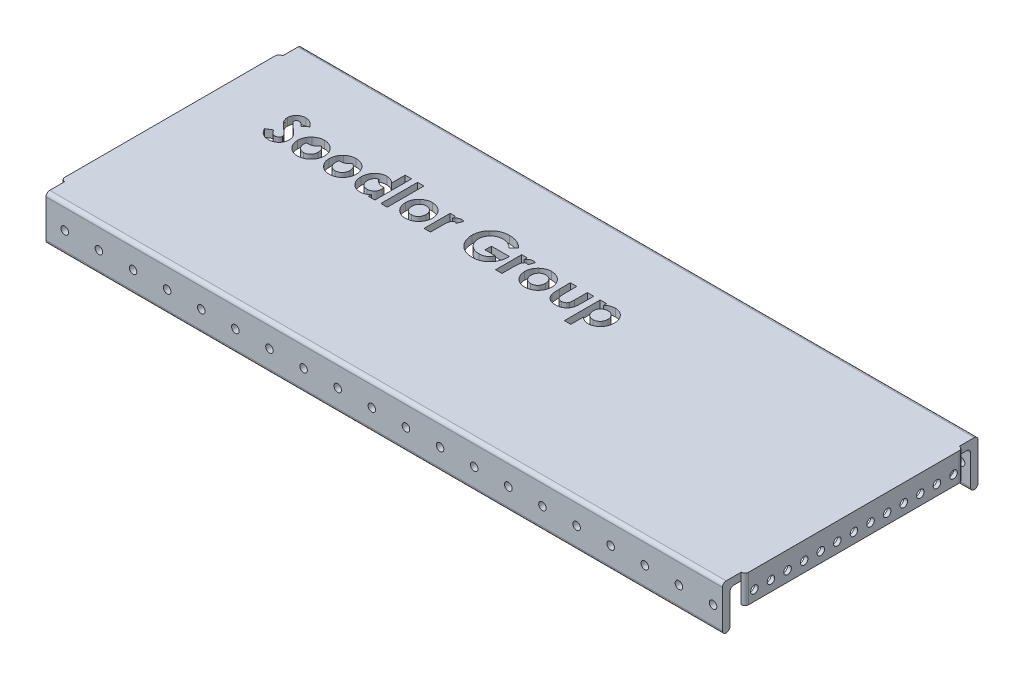
SolidWorks part; units mm, degrees
ref_plane "Front Plane" through (0, 0, 0) normal (0, 0, 1) x (1, 0, 0)
ref_plane "Top Plane" through (0, 0, 0) normal (0, 1, 0) x (1, 0, 0)
ref_plane "Right Plane" through (0, 0, 0) normal (1, 0, 0) x (0, 0, -1)
sketch "Sketch1" plane through (0, 0, 0) normal (0, 1, 0) x (1, 0, 0)
  line L1 (-180, 68.01) -> (180, 68.01)
  line L2 (-180, 68.01) -> (-180, -68.01)
  line L3 (-180, -68.01) -> (180, -68.01)
  line L4 (180, 68.01) -> (180, -68.01)
  line L5 (-180, 68.01) -> (180, -68.01) construction
  line L6 (-180, -68.01) -> (180, 68.01) construction
  point P0 (0, 0)
  dimension "D1" = 136.02
  dimension "D2" = 360
extrude "Boss-Extrude1" add sketch "Sketch1" along normal blind 4
sketch "Sketch2" plane through (0, 0, 0) normal (0, -1, 0) x (-1, 0, 0)
  line L0 (-180, -68.01) -> (-180, 68.01) construction
  line L1 (180, -68.01) -> (-180, -68.01)
  line L2 (180, -68.01) -> (180, -64.01)
  line L3 (180, -64.01) -> (-180, -64.01)
  line L4 (-180, -68.01) -> (-180, -64.01)
  line L6 (180, 68.01) -> (-180, 68.01)
  line L7 (180, 68.01) -> (180, 64.01)
  line L8 (180, 64.01) -> (-180, 64.01)
  line L9 (-180, 68.01) -> (-180, 64.01)
  dimension "D1" = 4
  dimension "D2" = 4
extrude "Boss-Extrude2" add sketch "Sketch2" along normal blind 20
fillet "Fillet1" radius 2 8 edges at (0, 0, -64.01) (0, 0, 64.01) (0, -20, 64.01) (0, -20, -64.01) (0, -20, -68.01) (0, -20, 68.01) (0, 4, -68.01) (0, 4, 68.01)
sketch "Sketch3" plane through (0, 0, -68.01) normal (0, 0, -1) x (-1, 0, 0)
  line L1 (180, 2) -> (-180, 2) construction
  line L2 (180, 2) -> (180, -18) construction
  line L3 (-180, 2) -> (-180, -18) construction
  circle A0 centre (-175, -8.5) radius 2.005
  circle A1 centre (-156.8421, -8.5) radius 2.005
  circle A2 centre (-138.6842, -8.5) radius 2.005
  circle A3 centre (-120.5263, -8.5) radius 2.005
  circle A4 centre (-102.3684, -8.5) radius 2.005
  circle A5 centre (-84.2105, -8.5) radius 2.005
  circle A6 centre (-66.0526, -8.5) radius 2.005
  circle A7 centre (-47.8947, -8.5) radius 2.005
  circle A8 centre (-29.7368, -8.5) radius 2.005
  circle A9 centre (-11.5789, -8.5) radius 2.005
  circle A10 centre (6.5789, -8.5) radius 2.005
  circle A11 centre (24.7368, -8.5) radius 2.005
  circle A12 centre (42.8947, -8.5) radius 2.005
  circle A13 centre (61.0526, -8.5) radius 2.005
  circle A14 centre (79.2105, -8.5) radius 2.005
  circle A15 centre (97.3684, -8.5) radius 2.005
  circle A16 centre (115.5263, -8.5) radius 2.005
  circle A17 centre (133.6842, -8.5) radius 2.005
  circle A18 centre (151.8421, -8.5) radius 2.005
  circle A19 centre (170, -8.5) radius 2.005
  dimension "D1" = 4.01
  dimension "D2" = 5
  dimension "D3" = 10.5
  dimension "D4" = 20
  dimension "D5" = 10
extrude "Cut-Extrude1" cut sketch "Sketch3" against normal through all
sketch "Sketch4" plane through (180, 0, 0) normal (1, 0, 0) x (0, 0, -1)
  line L0 (-66.01, 4) -> (66.01, 4) construction
  line L1 (-58.01, 4) -> (58.01, 4)
  line L2 (-58.01, 4) -> (-58.01, -11)
  line L3 (-58.01, -11) -> (58.01, -11)
  line L4 (58.01, 4) -> (58.01, -11)
  line L5 (-68.01, 2) -> (-68.01, -18) construction
  line L6 (68.01, 2) -> (68.01, -18) construction
  line L7 (-62.01, 0) -> (62.01, 0) construction
  circle A0 centre (-53.01, -5.5) radius 2.005
  circle A1 centre (-44.175, -5.5) radius 2.005
  circle A2 centre (-35.34, -5.5) radius 2.005
  circle A3 centre (-26.505, -5.5) radius 2.005
  circle A4 centre (-17.67, -5.5) radius 2.005
  circle A5 centre (-8.835, -5.5) radius 2.005
  circle A6 centre (0, -5.5) radius 2.005
  circle A7 centre (8.835, -5.5) radius 2.005
  circle A8 centre (17.67, -5.5) radius 2.005
  circle A9 centre (26.505, -5.5) radius 2.005
  circle A10 centre (35.34, -5.5) radius 2.005
  circle A11 centre (44.175, -5.5) radius 2.005
  circle A12 centre (53.01, -5.5) radius 2.005
  dimension "D5" = 4.01
  dimension "D1" = 10
  dimension "D2" = 10
  dimension "D3" = 15
  dimension "D4" = 5.5
  dimension "D6" = 5
  dimension "D8" = 5
  dimension "D7" = 13
extrude "Boss-Extrude3" add sketch "Sketch4" along normal blind 2
fillet "Fillet2" radius 2 2 edges at (182, -3.5, 58.01) (182, -3.5, -58.01)
sketch "Sketch5" plane through (0, 4, 0) normal (0, 1, 0) x (1, 0, 0)
  line L0 (0, 66.01) -> (0, -66.01) construction
  line L1 (180, 66.01) -> (-180, 66.01) construction
  line L2 (-180, -66.01) -> (180, -66.01) construction
sketch "Sketch6" plane through (-180, 0, 0) normal (-1, 0, 0) x (0, 0, 1)
  line L0 (68.01, 2) -> (68.01, -18) construction
  line L1 (-58.01, 4) -> (58.01, 4)
  line L2 (-58.01, 4) -> (-58.01, -11)
  line L3 (-58.01, -11) -> (58.01, -11)
  line L4 (58.01, 4) -> (58.01, -11)
  circle A0 centre (-53.01, -5.5) radius 2.005
  circle A1 centre (-44.175, -5.5) radius 2.005
  circle A2 centre (-35.34, -5.5) radius 2.005
  circle A3 centre (-26.505, -5.5) radius 2.005
  circle A4 centre (-17.67, -5.5) radius 2.005
  circle A5 centre (-8.835, -5.5) radius 2.005
  circle A6 centre (0, -5.5) radius 2.005
  circle A7 centre (8.835, -5.5) radius 2.005
  circle A8 centre (17.67, -5.5) radius 2.005
  circle A9 centre (26.505, -5.5) radius 2.005
  circle A10 centre (35.34, -5.5) radius 2.005
  circle A11 centre (44.175, -5.5) radius 2.005
  circle A12 centre (53.01, -5.5) radius 2.005
  dimension "D4" = 4.01
  dimension "D6" = 5
  dimension "D1" = 15
  dimension "D2" = 10
  dimension "D3" = 5
  dimension "D5" = 13
extrude "Boss-Extrude4" add sketch "Sketch6" along normal blind 2
fillet "Fillet3" radius 2 2 edges at (-182, -3.5, 58.01) (-182, -3.5, -58.01)
sketch "Sketch7" plane through (0, 4, 0) normal (0, 1, 0) x (1, 0, 0)
  line L0 (-182, 16.01) -> (45.6008, 16.01) construction
  line L1 (-182, -56.01) -> (-182, 56.01) construction
  line L2 (180, 66.01) -> (-180, 66.01) construction
  text T0 "<b>Soodlor Group</b>" font "Century Gothic" height in points 72
  dimension "D1" = 50
  dimension "D2" = 30
extrude "Cut-Extrude2" cut sketch "Sketch7" against normal blind 10
sketch "Sketch8" plane through (0, 4, 0) normal (0, 1, 0) x (1, 0, 0)
  circle A0 centre (-149.9811, 29.5415) radius 5.0523
  circle A1 centre (-132.7328, 29.5415) radius 5.4129
  circle A2 centre (-116.0745, 29.5415) radius 4.9578
  circle A3 centre (-93.0701, 29.5415) radius 5.3287
  circle A4 centre (-28.8166, 29.5415) radius 6.2082
  circle A5 centre (3.9051, 29.5415) radius 5.4165
extrude "Cut-Extrude3" cut sketch "Sketch8" against normal blind 10
